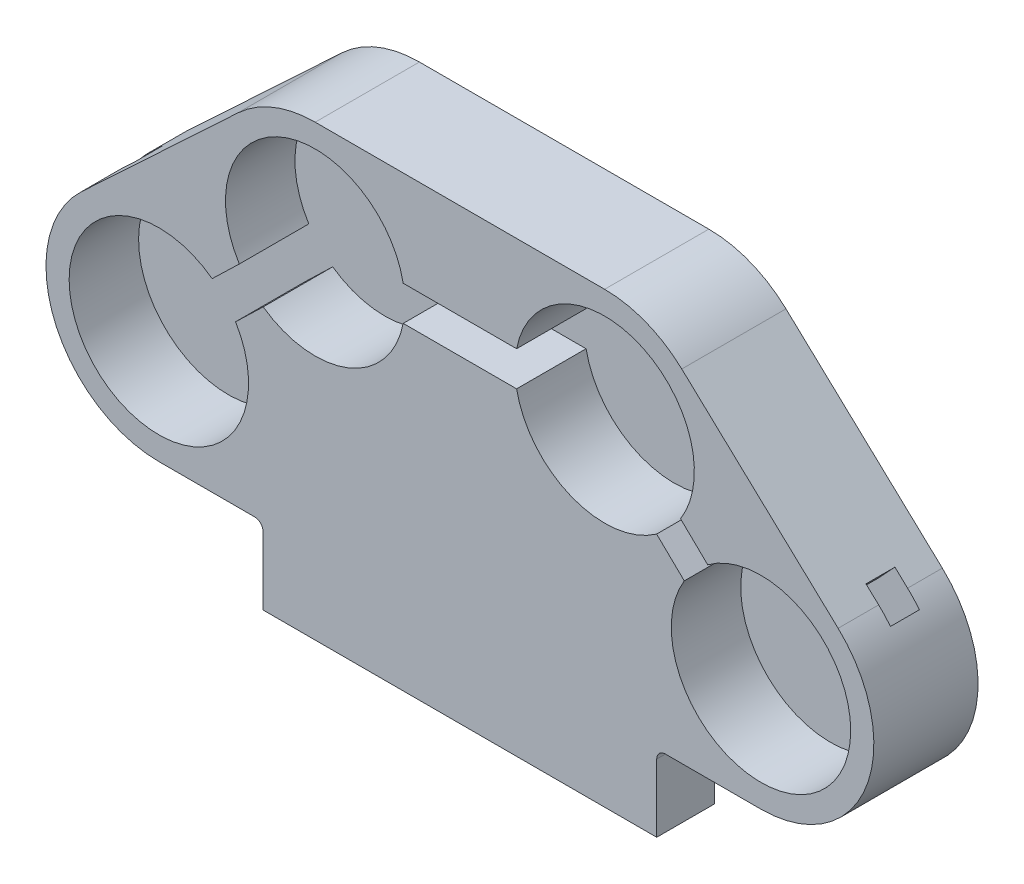
SolidWorks part; units mm, degrees
ref_plane "Front Plane" through (0, 0, 0) normal (0, 0, 1) x (1, 0, 0)
ref_plane "Top Plane" through (0, 0, 0) normal (0, 1, 0) x (1, 0, 0)
ref_plane "Right Plane" through (0, 0, 0) normal (1, 0, 0) x (0, 0, -1)
sketch "Sketch1" plane through (0, 0, 0) normal (0, 0, 1) x (1, 0, 0)
  line L0 (-11.9595, 12.7758) -> (-50.7466, -23.5332) construction
  line L1 (11.9595, 12.7758) -> (50.7466, -23.5332) construction
  line L2 (-11.9595, 12.7758) -> (11.9595, 12.7758) construction
  line L3 (-50.7466, -23.5332) -> (50.7466, -23.5332) construction
  line L4 (-17.5, -2) -> (17.5, -2) construction
  line L5 (0, 0) -> (0, -2) construction
  line L6 (-17.5, -2) -> (-17.5, 4) construction
  line L7 (-17.5, 4) -> (-20.5, 4) construction
  line L8 (-20.5, 4) -> (-20.5, -5) construction
  line L9 (-20.5, -5) -> (20.5, -5) construction
  line L10 (20.5, -5) -> (20.5, 4) construction
  line L11 (20.5, 4) -> (17.5, 4) construction
  line L12 (17.5, 4) -> (17.5, -2) construction
  line L13 (0, -2) -> (0, 40.1846) construction
  line L14 (-26.0058, 14.352) -> (-12.5, 26.995) construction
  line L15 (-32.669, 21.47) -> (-19.1632, 34.1129)
  line L16 (-26.0058, 4.602) -> (-17.75, 4.602)
  line L17 (-17, 3.852) -> (-17, -2)
  line L18 (-17, -2) -> (0, -2)
  line L19 (-12.5, 36.745) -> (0, 36.745)
  line L20 (0, 36.745) -> (0, -2)
  circle A0 centre (0, 0) radius 17.5 construction
  circle A1 centre (-26.0058, 14.352) radius 7.75
  circle A2 centre (-12.5, 26.995) radius 7.75
  circle A3 centre (-12.5, 26.995) radius 9.75 construction
  circle A4 centre (-26.0058, 14.352) radius 9.75 construction
  arc A5 (-17.75, 4.602) -> (-17, 3.852) centre (-17.75, 3.852) cw
  arc A6 (-19.1632, 34.1129) -> (-12.5, 36.745) centre (-12.5, 26.995) cw
  arc A7 (-26.0058, 4.602) -> (-32.669, 21.47) centre (-26.0058, 14.352) cw
  dimension "D1" = 35
  dimension "D8" = 15.5
  dimension "D10" = 3
  dimension "D11" = 2
  dimension "D13" = 0.75
  dimension "D2" = 93.78
  dimension "D3" = 35
  dimension "2" = 2
  dimension "D4" = 6
  dimension "D5" = 3
  dimension "D6" = 3
  dimension "D7" = 3
  dimension "D9" = 25
  dimension "D12" = 0.5
extrude "Boss-Extrude1" add sketch "Sketch1" along normal blind 5 contours A7 L16 A5 L17 L18 L20 L19 A6 L15 A2 A1 region at (-12.1141, 15.2891, 0)
mirror "Mirror1" about plane through (0, 0, 0) normal (1, 0, 0) of "Boss-Extrude1"
sketch "Sketch3" plane through (0, 0, 0) normal (0, 0, -1) x (-1, 0, 0)
  line L0 (32.669, 21.47) -> (19.1632, 34.1129) construction
  line L1 (32.669, 21.47) -> (19.1632, 34.1129)
  line L2 (12.5, 36.745) -> (-12.5, 36.745) construction
  line L3 (12.5, 36.745) -> (-12.5, 36.745)
  line L4 (-32.669, 21.47) -> (-19.1632, 34.1129) construction
  line L5 (-32.669, 21.47) -> (-19.1632, 34.1129)
  line L6 (-19.3426, 7.2341) -> (-5.8368, 19.877)
  line L7 (19.3426, 7.2341) -> (5.8368, 19.877)
  arc A0 (26.0058, 4.602) -> (32.669, 21.47) centre (26.0058, 14.352) ccw construction
  arc A1 (26.0058, 4.602) -> (32.669, 21.47) centre (26.0058, 14.352) ccw construction
  arc A2 (19.1632, 34.1129) -> (12.5, 36.745) centre (12.5, 26.995) ccw construction
  arc A3 (19.1632, 34.1129) -> (12.5, 36.745) centre (12.5, 26.995) ccw
  arc A4 (-12.5, 36.745) -> (-19.1632, 34.1129) centre (-12.5, 26.995) ccw construction
  arc A5 (-12.5, 36.745) -> (-19.1632, 34.1129) centre (-12.5, 26.995) ccw
  arc A6 (-32.669, 21.47) -> (-26.0058, 4.602) centre (-26.0058, 14.352) ccw construction
  arc A7 (-32.669, 21.47) -> (-26.0058, 4.602) centre (-26.0058, 14.352) ccw construction
  circle A8 centre (-26.0058, 14.352) radius 9.75 construction
  circle A9 centre (-12.5, 26.995) radius 9.75 construction
  circle A10 centre (12.5, 26.995) radius 9.75 construction
  circle A11 centre (26.0058, 14.352) radius 9.75 construction
  circle A12 centre (0, 13.6418) radius 8.5409 construction
  arc A13 (-5.8368, 19.877) -> (5.8368, 19.877) centre (0, 13.6418) cw
  arc A14 (-32.669, 21.47) -> (-19.3426, 7.2341) centre (-26.0058, 14.352) ccw
  arc A15 (32.669, 21.47) -> (19.3426, 7.2341) centre (26.0058, 14.352) cw
  arc M9 (26.0058, 4.602) -> (32.669, 21.47) centre (26.0058, 14.352) ccw
  line M10 (32.669, 21.47) -> (19.1632, 34.1129)
  arc M11 (19.1632, 34.1129) -> (12.5, 36.745) centre (12.5, 26.995) ccw
  line M12 (12.5, 36.745) -> (-12.5, 36.745)
  arc M13 (-12.5, 36.745) -> (-19.1632, 34.1129) centre (-12.5, 26.995) ccw
  line M14 (-19.1632, 34.1129) -> (-32.669, 21.47)
  arc M15 (-32.669, 21.47) -> (-26.0058, 4.602) centre (-26.0058, 14.352) ccw
  circle M23 centre (12.5, 26.995) radius 7.75
  circle M24 centre (26.0058, 14.352) radius 7.75
  circle M25 centre (-12.5, 26.995) radius 7.75
  circle M26 centre (-26.0058, 14.352) radius 7.75
extrude "Boss-Extrude2" add sketch "Sketch3" along normal blind 4 contours A15 A14 L6 A13 L7 M9 M10 M11 M12 M13 M14 M15 M23 M25 M26 M24 | M26 | M25 | M23 | M24 region at (0, 22.5292, 0) region at (-12.5, 26.995, 0) region at (-26.0058, 14.352, 0) region at (12.5, 26.995, 0) region at (26.0058, 14.352, 0)
sketch "Sketch4" plane through (0, 0, 0) normal (0, 0, 1) x (1, 0, 0)
  circle A0 centre (26.0058, 14.352) radius 7.75 construction
  circle A1 centre (12.5, 26.995) radius 7.75 construction
  circle A2 centre (-12.5, 26.995) radius 7.75 construction
  circle A3 centre (-26.0058, 14.352) radius 7.75 construction
  circle A4 centre (26.0058, 14.352) radius 7.75
  circle A5 centre (12.5, 26.995) radius 7.75
  circle A6 centre (-12.5, 26.995) radius 7.75
  circle A7 centre (-26.0058, 14.352) radius 7.75
extrude "Cut-Extrude1" cut sketch "Sketch4" against normal blind 1
sketch "Sketch5" plane through (0, 0, 5) normal (0, 0, 1) x (1, 0, 0)
  line L0 (-26.0058, 14.352) -> (-12.5, 26.995) construction
  line L1 (-17.1499, 24.6966) -> (-23.3682, 18.6909)
  line L2 (-23.3682, 18.6909) -> (-21.284, 16.533)
  line L3 (-21.284, 16.533) -> (-15.0658, 22.5387)
  line L4 (-15.0658, 22.5387) -> (-17.1499, 24.6966)
  line L5 (0, 0) -> (0, 28.253) construction
  line L6 (-12.5, 26.995) -> (12.5, 26.995) construction
  line L7 (-6.9065, 28.495) -> (8.5226, 28.495)
  line L8 (8.5226, 28.495) -> (8.5226, 25.495)
  line L9 (8.5226, 25.495) -> (-6.9065, 25.495)
  line L10 (-6.9065, 25.495) -> (-6.9065, 28.495)
  line L11 (21.284, 16.533) -> (15.0658, 22.5387)
  line L12 (23.3682, 18.6909) -> (21.284, 16.533)
  line L13 (17.1499, 24.6966) -> (23.3682, 18.6909)
  line L14 (15.0658, 22.5387) -> (17.1499, 24.6966)
  point P6 (-16.1078, 23.6176)
  point P16 (-6.9065, 26.995)
  dimension "D1" = 3
  dimension "D2" = 3
extrude "Cut-Extrude2" cut sketch "Sketch5" against normal up to surface (6 mm away) up to face at (-18.2558, 14.352, -1)
sketch "Sketch6" plane through (-25.9692, 27.7416, 0) normal (-0.6834, 0.73, 0) x (0.73, 0.6834, 0)
  line L0 (-16.9271, 1) -> (-1.556, 1) construction
  line L1 (-16.9271, 1) -> (-1.556, 1) construction
  line L2 (-9.1771, -5) -> (-9.1771, 4) construction
  line L3 (-7.6771, 1) -> (-10.6771, 1)
  line L4 (-7.6771, 1) -> (-7.6771, -1.5)
  line L5 (-7.6771, -1.5) -> (-10.6771, -1.5)
  line L6 (-10.6771, 1) -> (-10.6771, -1.5)
  point P6 (-11.5737, 1)
  point P7 (-10.6748, 1)
  point P8 (-9.1771, 1)
  dimension "D1" = 2.5
  dimension "D2" = 3
extrude "Cut-Extrude3" cut sketch "Sketch6" against normal blind 11
mirror "Mirror2" about plane through (0, 0, 0) normal (1, 0, 0) of "Cut-Extrude3"
